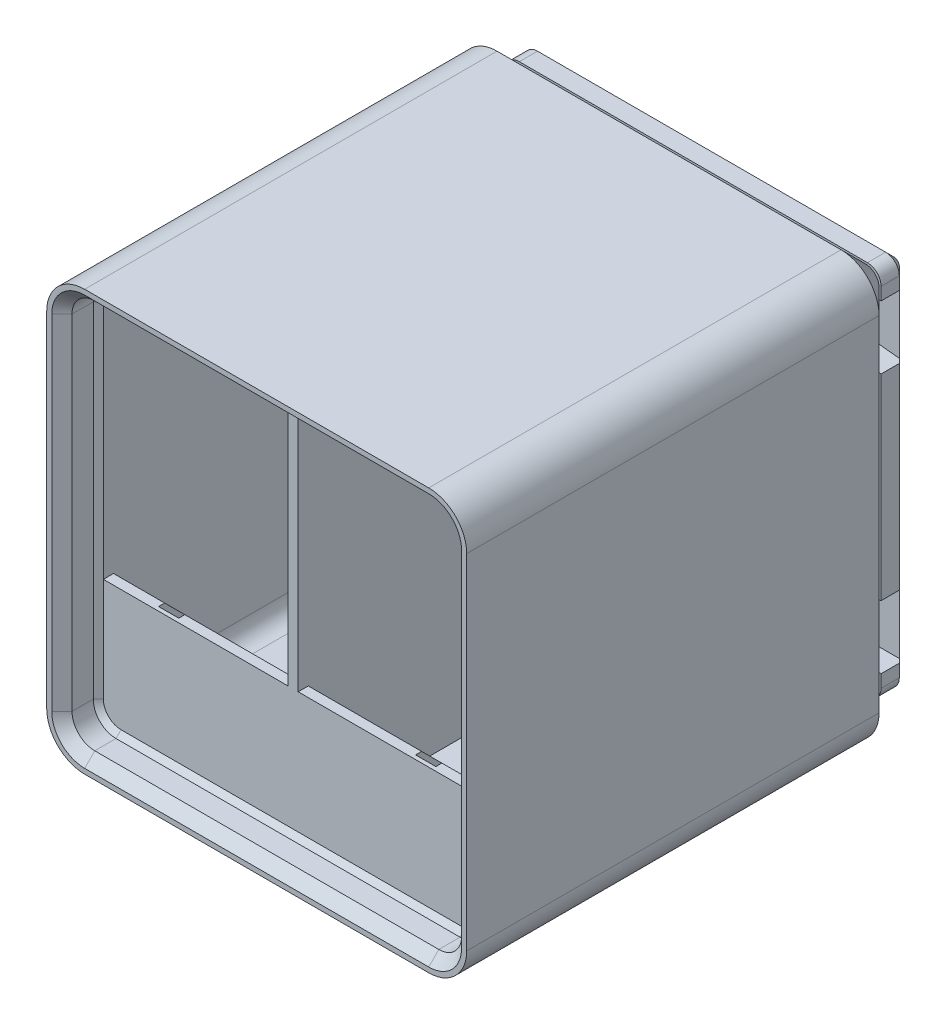
SolidWorks part; units mm, degrees
ref_plane "Front Plane" through (0, 0, 0) normal (0, 0, 1) x (1, 0, 0)
ref_plane "Top Plane" through (0, 0, 0) normal (0, 1, 0) x (1, 0, 0)
ref_plane "Right Plane" through (0, 0, 0) normal (1, 0, 0) x (0, 0, -1)
sketch "Sketch1" plane through (0, 0, 0) normal (0, 0, 1) x (1, 0, 0)
  line L1 (18.55, 18.55) -> (-18.55, 18.55)
  line L2 (18.55, 18.55) -> (18.55, -18.55)
  line L3 (18.55, -18.55) -> (-18.55, -18.55)
  line L4 (-18.55, 18.55) -> (-18.55, -18.55)
  line L5 (18.55, 18.55) -> (-18.55, -18.55) construction
  line L6 (18.55, -18.55) -> (-18.55, 18.55) construction
  point P0 (0, 0)
  dimension "D1" = 37.1
extrude "Boss-Extrude1" add sketch "Sketch1" along normal blind 2.6
sketch "Sketch2" plane through (0, 0, 2.6) normal (0, 0, 1) x (1, 0, 0)
  line L1 (-20.75, 20.75) -> (20.75, 20.75)
  line L2 (-20.75, 20.75) -> (-20.75, -20.75)
  line L3 (-20.75, -20.75) -> (20.75, -20.75)
  line L4 (20.75, 20.75) -> (20.75, -20.75)
  line L5 (-20.75, 20.75) -> (20.75, -20.75) construction
  line L6 (-20.75, -20.75) -> (20.75, 20.75) construction
  point P0 (0, 0)
  dimension "D1" = 41.5
extrude "Boss-Extrude2" add sketch "Sketch2" along normal blind 2.4
sketch "Sketch8" plane through (0, 0, 2.6) normal (0, 0, -1) x (-1, 0, 0)
  line L0 (-18.55, 18.55) -> (-18.55, 5.0094) construction
  line L1 (-18.55, -18.55) -> (-18.55, 18.55) construction
  line L2 (-14.65, 10.1) -> (-18.55, 9.7)
  line L11 (-12.7, 15.95) -> (-18.55, 15.95)
  line L12 (-12.7, 12.7) -> (-12.7, -12.7)
  line L13 (-12.7, -12.7) -> (12.7, -12.7)
  line L14 (12.7, -12.7) -> (12.7, 12.7)
  line L15 (12.7, 12.7) -> (-12.7, 12.7)
  line L16 (-12.7, 9.45) -> (-12.7, -12.7) construction
  line L22 (-18.55, 15.95) -> (-18.55, 9.7)
  arc A0 (-12.7, 15.95) -> (-12.7, 9.45) centre (-12.7, 12.7) cw
  arc A1 (-12.7, 9.45) -> (-14.65, 10.1) centre (-12.7, 12.7) cw
  dimension "D4" = 5.85
  dimension "D5" = 6.25
  dimension "D2" = 6.5
  dimension "D1" = 8.05
extrude "Base Magnet Slot" cut sketch "Sketch8" against normal blind 0.4 and the other way blind 2.2
sketch "Sketch12" plane through (0, 0, 0) normal (0, 0, -1) x (-1, 0, 0)
  line L0 (-12.7, 12.7) -> (-6.2, 12.7) construction
  line L1 (-12.7, 13.7) -> (-6.2, 13.7)
  line L2 (-12.7, 11.7) -> (-6.2, 11.7)
  arc A8 (-14.65, 10.1) -> (-12.7, 15.95) centre (-12.7, 12.7) ccw construction
  arc A9 (-14.65, 10.1) -> (-12.7, 15.95) centre (-12.7, 12.7) ccw construction
  arc A10 (-12.7, 13.7) -> (-12.7, 11.7) centre (-12.7, 12.7) ccw
  arc A11 (-6.2, 11.7) -> (-6.2, 13.7) centre (-6.2, 12.7) ccw
  point P3 (-9.45, 12.7)
  dimension "D1" = 2
  dimension "D2" = 6.5
extrude "Cut-Extrude1" cut sketch "Sketch12" against normal up to surface (2.6 mm away) up to face at (0, 0, 2.6)
mirror "Mirror1" about plane through (0, 0, 0) normal (0, 1, 0) of "Cut-Extrude1", "Base Magnet Slot"
mirror "Mirror2" about plane through (0, 0, 0) normal (1, 0, 0) of "Mirror1"
fillet "Fillet1" radius 1.35 4 edges at (18.55, 18.55, 1.3) (18.55, -18.55, 1.3) (-18.55, -18.55, 1.3) (-18.55, 18.55, 1.3)
fillet "Fillet2" radius 3.75 4 edges at (20.75, -20.75, 3.8) (20.75, 20.75, 3.8) (-20.75, -20.75, 3.8) (-20.75, 20.75, 3.8)
chamfer "Chamfer1" distance 0.8 angle 45 8 edges at (-18.1546, 18.1546, 0) (-18.55, 0, 0) (-18.1546, -18.1546, 0) (0, -18.55, 0) (18.1546, -18.1546, 0) (18.55, 0, 0) (18.1546, 18.1546, 0) (0, 18.55, 0)
chamfer "Chamfer2" distance 2.4 angle 45 8 edges at (20.75, 0, 2.6) (19.6517, 19.6517, 2.6) (19.6517, -19.6517, 2.6) (0, 20.75, 2.6) (0, -20.75, 2.6) (-19.6517, 19.6517, 2.6) (-19.6517, -19.6517, 2.6) (-20.75, 0, 2.6)
sketch "Sketch5" plane through (0, 0, 5) normal (0, 0, 1) x (1, 0, 0)
  line L32 (-17, -18.75) -> (17, -18.75)
  line L33 (18.75, -17) -> (18.75, 17)
  line L42 (17, 18.75) -> (-17, 18.75)
  line L56 (-18.75, 17) -> (-18.75, -17)
  line L57 (-17, -20.75) -> (17, -20.75)
  line L58 (20.75, -17) -> (20.75, 17)
  line L59 (17, 20.75) -> (-17, 20.75)
  line L60 (-20.75, 17) -> (-20.75, -17)
  line L61 (-17, -20.75) -> (17, -20.75)
  line L62 (20.75, -17) -> (20.75, 17)
  line L63 (17, 20.75) -> (-17, 20.75)
  line L64 (-20.75, 17) -> (-20.75, -17)
  arc A24 (17, -18.75) -> (18.75, -17) centre (17, -17) ccw
  arc A25 (18.75, 17) -> (17, 18.75) centre (17, 17) ccw
  arc A26 (-17, 18.75) -> (-18.75, 17) centre (-17, 17) ccw
  arc A27 (-18.75, -17) -> (-17, -18.75) centre (-17, -17) ccw
  arc A30 (17, -20.75) -> (20.75, -17) centre (17, -17) ccw
  arc A31 (20.75, 17) -> (17, 20.75) centre (17, 17) ccw
  arc A32 (-17, 20.75) -> (-20.75, 17) centre (-17, 17) ccw
  arc A33 (-20.75, -17) -> (-17, -20.75) centre (-17, -17) ccw
  arc A34 (17, -20.75) -> (20.75, -17) centre (17, -17) ccw
  arc A35 (20.75, 17) -> (17, 20.75) centre (17, 17) ccw
  arc A36 (-17, 20.75) -> (-20.75, 17) centre (-17, 17) ccw
  arc A37 (-20.75, -17) -> (-17, -20.75) centre (-17, -17) ccw
  dimension "D1" = 0
  dimension "D2" = 2
extrude "Side Walls" add sketch "Sketch5" along normal blind 36.85
sketch "Sketch11" plane through (0, 0, 41.85) normal (0, 0, 1) x (1, 0, 0)
  line L24 (-17, -20.75) -> (17, -20.75) construction
  line L25 (20.75, -17) -> (20.75, 17) construction
  line L26 (17, 20.75) -> (-17, 20.75) construction
  line L27 (-20.75, 17) -> (-20.75, -17) construction
  line L28 (-17, -20.75) -> (17, -20.75)
  line L29 (20.75, -17) -> (20.75, 17)
  line L30 (17, 20.75) -> (-17, 20.75)
  line L31 (-20.75, 17) -> (-20.75, -17)
  line L32 (-17, -19.25) -> (17, -19.25)
  line L33 (19.25, -17) -> (19.25, 17)
  line L34 (17, 19.25) -> (-17, 19.25)
  line L35 (-19.25, 17) -> (-19.25, -17)
  arc A24 (-20.75, -17) -> (-17, -20.75) centre (-17, -17) ccw construction
  arc A25 (17, -20.75) -> (20.75, -17) centre (17, -17) ccw construction
  arc A26 (20.75, 17) -> (17, 20.75) centre (17, 17) ccw construction
  arc A27 (-17, 20.75) -> (-20.75, 17) centre (-17, 17) ccw construction
  arc A28 (-20.75, -17) -> (-17, -20.75) centre (-17, -17) ccw
  arc A29 (17, -20.75) -> (20.75, -17) centre (17, -17) ccw
  arc A30 (20.75, 17) -> (17, 20.75) centre (17, 17) ccw
  arc A31 (-17, 20.75) -> (-20.75, 17) centre (-17, 17) ccw
  arc A32 (17, -19.25) -> (19.25, -17) centre (17, -17) ccw
  arc A33 (19.25, 17) -> (17, 19.25) centre (17, 17) ccw
  arc A34 (-17, 19.25) -> (-19.25, 17) centre (-17, 17) ccw
  arc A35 (-19.25, -17) -> (-17, -19.25) centre (-17, -17) ccw
extrude "Boss-Extrude4" add sketch "Sketch11" along normal blind 3.9
chamfer "Chamfer3" distance 0.8 angle 45 8 edges at (0, -19.25, 41.85) (18.591, -18.591, 41.85) (-18.591, -18.591, 41.85) (19.25, 0, 41.85) (-19.25, 0, 41.85) (18.591, 18.591, 41.85) (-18.591, 18.591, 41.85) (0, 19.25, 41.85)
chamfer "Chamfer4" distance 1 angle 45 8 edges at (0, -19.25, 45.75) (18.591, -18.591, 45.75) (-18.591, -18.591, 45.75) (19.25, 0, 45.75) (-19.25, 0, 45.75) (18.591, 18.591, 45.75) (-18.591, 18.591, 45.75) (0, 19.25, 45.75)
sketch "Sketch13" plane through (18.75, 0, 0) normal (-1, 0, 0) x (0, 0, 1)
  line L0 (5, -17) -> (5, 17) construction
  line L1 (42.15, 18.75) -> (5, 18.75) construction
  line L2 (5, -1.25) -> (5, 18.75)
  line L3 (25, 18.75) -> (5, 18.75)
  arc A0 (25, 18.75) -> (5, -1.25) centre (25, -1.25) ccw
  dimension "D1" = 20
extrude "Internal Ramp" add sketch "Sketch13" along normal up to surface (37.5 mm away) up to face at (-18.75, 0, 23.575)
ref_plane "Plane1" through (0, 0, 42.15) normal (0, 0, -1) x (-1, 0, 0)
sketch "Sketch14" plane through (0, 0, 42.15) normal (0, 0, -1) x (-1, 0, 0)
  line L0 (-18.75, -17) -> (-18.75, 17) construction
  line L1 (17, -18.75) -> (-17, -18.75) construction
  line L2 (18.75, 17) -> (18.75, -17) construction
  line L3 (-18.75, -17) -> (-18.75, -6.75)
  line L4 (17, -18.75) -> (-17, -18.75)
  line L5 (18.75, -6.75) -> (18.75, -17)
  line L6 (-18.75, -6.75) -> (18.75, -6.75)
  arc A0 (-18.75, -17) -> (-17, -18.75) centre (-17, -17) ccw construction
  arc A1 (17, -18.75) -> (18.75, -17) centre (17, -17) ccw construction
  arc A2 (-18.75, -17) -> (-17, -18.75) centre (-17, -17) ccw
  arc A3 (17, -18.75) -> (18.75, -17) centre (17, -17) ccw
  dimension "D1" = 12
extrude "Boss-Extrude6" add sketch "Sketch14" along normal blind 12
chamfer "Chamfer5" distance 11 angle 45 1 edges at (0, -6.75, 30.15)
ref_plane "Offset Plane" through (0, 0, 41.75) normal (0, 0, 1) x (1, 0, 0)
sketch "Sketch17" plane through (0, 0, 41.75) normal (0, 0, 1) x (1, 0, 0)
  line L0 (-17, -20.75) -> (17, -20.75) construction
  line L1 (-17, -20.75) -> (17, -20.75) construction
  line L2 (-20.75, -12.7) -> (20.75, -12.7) construction
  line L3 (-20.75, 17) -> (-20.75, -17) construction
  line L4 (20.75, -17) -> (20.75, 17) construction
  line L5 (-20.75, 17) -> (-20.75, -17) construction
  line L6 (-12.7, -11.0494) -> (-12.7, 18.75) construction
  line L7 (-17, 18.75) -> (17, 18.75) construction
  line L8 (-15.95, -12.7) -> (-15.95, -20.75)
  line L9 (-15.95, -20.75) -> (-9.45, -20.75)
  line L10 (-10.1, -14.65) -> (-9.45, -20.75)
  line L11 (-12.7, -12.7) -> (-12.7, -4.7) construction
  line L13 (-13.7, -9.6077) -> (-13.7, -4.7)
  line L14 (-11.7, -9.6077) -> (-11.7, -4.7)
  arc A0 (-15.95, -12.7) -> (-13.7, -9.6077) centre (-12.7, -12.7) cw
  arc A2 (-11.7, -4.7) -> (-13.7, -4.7) centre (-12.7, -4.7) ccw
  arc A3 (-11.7, -9.6077) -> (-10.1, -14.65) centre (-12.7, -12.7) cw
  point P20 (-12.7, -8.7)
  dimension "D3" = 3.25
  dimension "D1" = 8.05
  dimension "D2" = 8.05
  dimension "D4" = 6.5
  dimension "D5" = 5.85
extrude "Cut-Extrude2" cut sketch "Sketch17" against normal blind 2.6
mirror "Mirror3" about plane through (0, 0, 0) normal (1, 0, 0) of "Cut-Extrude2"
sketch "Sketch18" plane through (0, 0, 0) normal (1, 0, 0) x (0, 0, -1)
  line L0 (-42.15, 18.75) -> (-42.15, 17) construction
  line L1 (-42.15, 18.75) -> (-25, 18.75) construction
  line L2 (-42.15, 18.75) -> (-42.15, 17)
  line L3 (-42.15, 18.75) -> (-25, 18.75)
  line L4 (-30.15, -18.75) -> (-30.15, -17.75) construction
  line L5 (-30.15, -17.75) -> (-30.9, -17) construction
  line L6 (-42.15, 17) -> (-42.15, -6.75)
  line L7 (-42.15, -6.75) -> (-41.15, -6.75)
  line L8 (-41.15, -6.75) -> (-30.9, -17)
  line L9 (-30.9, -17) -> (-5, -17)
  line L10 (-5, -17) -> (-5, -1.25)
  line L11 (-16.8185, 17) -> (-42.15, 17)
  line L12 (-42.15, 17) -> (-42.15, -6.75)
  line L13 (-42.15, -6.75) -> (-41.15, -6.75)
  line L17 (-30.9, -17) -> (-41.15, -6.75) construction
  line L18 (-30.15, -18.75) -> (-30.15, -17.75)
  line L19 (-30.15, -17.75) -> (-30.9, -17)
  line L20 (-30.9, -17) -> (-41.15, -6.75)
  line L21 (-30.15, -18.75) -> (-5, -18.75) construction
  line L22 (-30.15, -18.75) -> (-5, -18.75)
  line L23 (-5, -17) -> (-5, -18.75) construction
  line L24 (-5, -17) -> (-5, -1.25) construction
  line L25 (-5, -17) -> (-5, -18.75)
  line L26 (-5, -17) -> (-5, -1.25)
  arc A0 (-16.8185, 17) -> (-25, 18.75) centre (-25, -1.25) ccw construction
  arc A1 (-5, -1.25) -> (-16.8185, 17) centre (-25, -1.25) ccw
  arc A3 (-5, -1.25) -> (-16.8185, 17) centre (-25, -1.25) ccw construction
  arc A4 (-16.8185, 17) -> (-25, 18.75) centre (-25, -1.25) ccw
  arc A5 (-5, -1.25) -> (-16.8185, 17) centre (-25, -1.25) ccw
  dimension "D1" = 0
extrude "Split Wall" add sketch "Sketch18" along normal mid plane 1
equation "\"MagnetHoleDia\"= 6.5"
equation "\"MagnetPressGap\"= 5.85"
equation "\"MagnetSlotDepth\"= 2.6"
equation "\"D2@Sketch17\"=\"D1@Sketch17\""
equation "\"D3@Sketch17\"=\"MagnetHoleDia\"/2"
